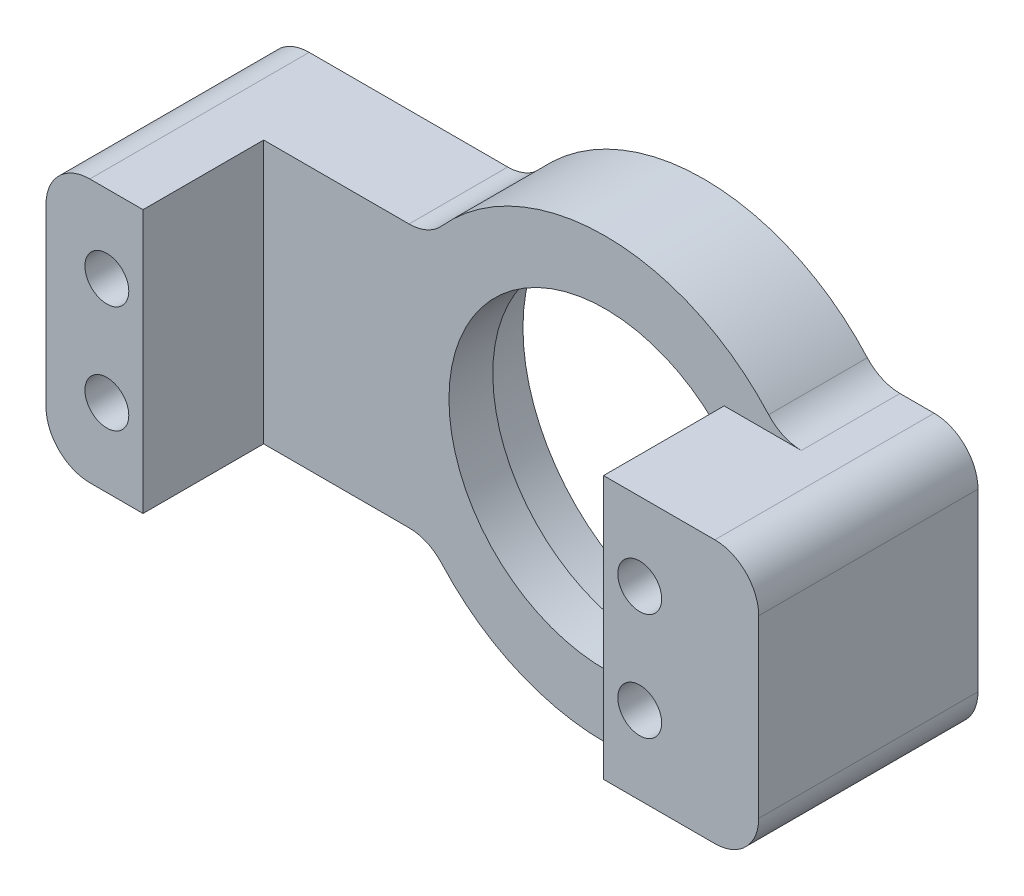
SolidWorks part; units mm, degrees
ref_plane "Front Plane" through (0, 0, 0) normal (0, 0, 1) x (1, 0, 0)
ref_plane "Top Plane" through (0, 0, 0) normal (0, 1, 0) x (1, 0, 0)
ref_plane "Right Plane" through (0, 0, 0) normal (1, 0, 0) x (0, 0, -1)
sketch "Sketch1" plane through (0, 0, 0) normal (0, 0, 1) x (1, 0, 0)
  line L0 (0, 113.0073) -> (17, 113.0073) construction
  line L1 (-40, 125.0073) -> (-16, 125.0073)
  line L2 (-40, 125.0073) -> (-40, 101.0073)
  line L3 (-40, 101.0073) -> (-16, 101.0073)
  line L4 (25, 125.0073) -> (25, 101.0073)
  line L6 (16, 125.0073) -> (25, 125.0073)
  line L8 (16, 101.0073) -> (25, 101.0073)
  arc A0 (16, 125.0073) -> (-16, 125.0073) centre (0, 113.0073) ccw
  circle A1 centre (0, 113.0073) radius 16.5
  arc A2 (-16, 101.0073) -> (16, 101.0073) centre (0, 113.0073) ccw
  dimension "D1" = 12
  dimension "D3" = 25
  dimension "D4" = 40
extrude "Boss-Extrude1" add sketch "Sketch1" along normal blind 5
sketch "Sketch2" plane through (0, 0, 5) normal (0, 0, 1) x (1, 0, 0)
  line L6 (-16, 125.0073) -> (-40, 125.0073)
  line L7 (-40, 125.0073) -> (-40, 101.0073)
  line L8 (-40, 101.0073) -> (-16, 101.0073)
  line L9 (16, 101.0073) -> (25, 101.0073)
  line L10 (25, 101.0073) -> (25, 125.0073)
  line L11 (25, 125.0073) -> (16, 125.0073)
  line L12 (-16, 125.0073) -> (-40, 125.0073)
  line L13 (-40, 125.0073) -> (-40, 101.0073)
  line L14 (-40, 101.0073) -> (-16, 101.0073)
  line L15 (16, 101.0073) -> (25, 101.0073)
  line L16 (25, 101.0073) -> (25, 125.0073)
  line L17 (25, 125.0073) -> (16, 125.0073)
  circle A0 centre (0, 113.0073) radius 14.25
  arc A2 (-16, 101.0073) -> (16, 101.0073) centre (0, 113.0073) ccw
  arc A3 (16, 125.0073) -> (-16, 125.0073) centre (0, 113.0073) ccw
  arc A4 (-16, 101.0073) -> (16, 101.0073) centre (0, 113.0073) ccw
  arc A5 (16, 125.0073) -> (-16, 125.0073) centre (0, 113.0073) ccw
  dimension "D1" = 0
extrude "Boss-Extrude2" add sketch "Sketch2" along normal blind 4
sketch "Sketch4" plane through (0, 0, 9) normal (0, 0, 1) x (1, 0, 0)
  line L0 (-40, 101.0073) -> (-16, 101.0073) construction
  line L1 (25, 101.0073) -> (10.85, 101.0073)
  line L2 (25, 101.0073) -> (25, 125.0073)
  line L3 (25, 125.0073) -> (10.85, 125.0073)
  line L4 (10.85, 101.0073) -> (10.85, 125.0073)
  line L5 (-40, 125.0073) -> (-31.15, 125.0073)
  line L6 (-40, 125.0073) -> (-40, 101.0073)
  line L7 (-40, 101.0073) -> (-31.15, 101.0073)
  line L8 (-31.15, 125.0073) -> (-31.15, 101.0073)
  line L11 (25, 125.0073) -> (16, 125.0073) construction
extrude "Boss-Extrude4" add sketch "Sketch4" along normal blind 11
fillet "Fillet1" radius 4 8 edges at (16, 125.0073, 4.5) (-16, 125.0073, 4.5) (-16, 101.0073, 4.5) (16, 101.0073, 4.5) (-40, 101.0073, 10) (-40, 125.0073, 10) (25, 125.0073, 10) (25, 101.0073, 10)
sketch "Sketch5" plane through (0, 0, 20) normal (0, 0, 1) x (1, 0, 0)
  circle A0 centre (-34.45, 108.1073) radius 2
  circle A1 centre (-34.45, 117.9073) radius 2
  circle A2 centre (14.15, 108.1073) radius 2
  circle A3 centre (14.15, 117.9073) radius 2
extrude "Cut-Extrude1" cut sketch "Sketch5" against normal blind 8
